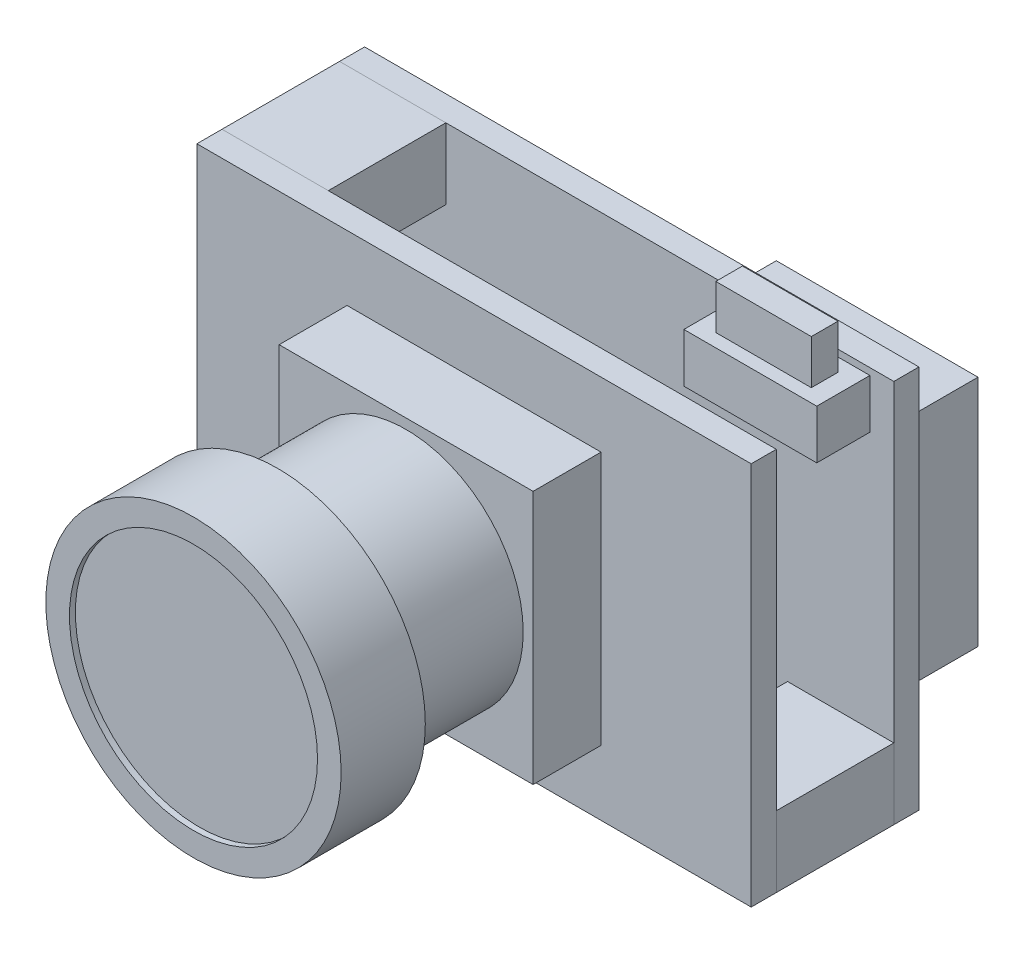
SolidWorks part; units mm, degrees
ref_plane "Front Plane" through (0, 0, 0) normal (0, 0, 1) x (1, 0, 0)
ref_plane "Top Plane" through (0, 0, 0) normal (0, 1, 0) x (1, 0, 0)
ref_plane "Right Plane" through (0, 0, 0) normal (1, 0, 0) x (0, 0, -1)
sketch "Sketch1" plane through (0, 0, 0) normal (0, 0, 1) x (1, 0, 0)
  line L1 (-9.385, 6.5) -> (9.385, 6.5)
  line L2 (-9.385, 6.5) -> (-9.385, -6.5)
  line L3 (-9.385, -6.5) -> (9.385, -6.5)
  line L4 (9.385, 6.5) -> (9.385, -6.5)
  line L5 (-9.385, 6.5) -> (9.385, -6.5) construction
  line L6 (-9.385, -6.5) -> (9.385, 6.5) construction
  point P0 (0, 0)
  dimension "D1" = 13
  dimension "D2" = 18.77
extrude "Boss-Extrude1" add sketch "Sketch1" along normal blind 0.85
sketch "Sketch2" plane through (0, 0, 0.85) normal (0, 0, 1) x (1, 0, 0)
  line L1 (9.385, -6.5) -> (5.785, -6.5)
  line L2 (9.385, -6.5) -> (9.385, -4.1)
  line L3 (9.385, -4.1) -> (5.785, -4.1)
  line L4 (5.785, -6.5) -> (5.785, -4.1)
  line L5 (-9.385, 6.5) -> (-5.785, 6.5)
  line L6 (-9.385, 6.5) -> (-9.385, 4.1)
  line L7 (-9.385, 4.1) -> (-5.785, 4.1)
  line L8 (-5.785, 6.5) -> (-5.785, 4.1)
  dimension "D1" = 2.4
  dimension "D2" = 3.6
extrude "Boss-Extrude2" add sketch "Sketch2" along normal blind 3.98 separate body
sketch "Sketch3" plane through (0, 0, 4.83) normal (0, 0, 1) x (1, 0, 0)
  line L0 (9.385, -6.5) -> (9.385, -4.1) construction
  line L1 (-9.385, 6.5) -> (9.385, 6.5)
  line L2 (-9.385, 6.5) -> (-9.385, -6.5)
  line L3 (-9.385, -6.5) -> (9.385, -6.5)
  line L4 (9.385, 6.5) -> (9.385, -6.5)
  line L5 (5.785, -6.5) -> (9.385, -6.5) construction
  point P4 (0, 0)
  point P6 (0, 0)
  point P8 (0, 0)
  point P9 (-9.385, 6.5)
  point P11 (-9.385, 6.5)
  point P13 (9.385, -6.5)
  point P16 (9.385, -6.5)
extrude "Boss-Extrude3" add sketch "Sketch3" along normal blind 0.85
sketch "Sketch4" plane through (0, 0, 5.68) normal (0, 0, 1) x (1, 0, 0)
  line L1 (-4.3, 4.3) -> (4.3, 4.3)
  line L2 (-4.3, 4.3) -> (-4.3, -4.3)
  line L3 (-4.3, -4.3) -> (4.3, -4.3)
  line L4 (4.3, 4.3) -> (4.3, -4.3)
  line L5 (-4.3, 4.3) -> (4.3, -4.3) construction
  line L6 (-4.3, -4.3) -> (4.3, 4.3) construction
  point P0 (0, 0)
  dimension "D1" = 8.6
extrude "Boss-Extrude4" add sketch "Sketch4" along normal blind 2.3
sketch "Sketch5" plane through (0, 0, 7.98) normal (0, 0, 1) x (1, 0, 0)
  circle A0 centre (0, 0) radius 3.965
  dimension "D1" = 7.93
extrude "Boss-Extrude5" add sketch "Sketch5" along normal blind 4.35
sketch "Sketch6" plane through (0, 0, 12.33) normal (0, 0, 1) x (1, 0, 0)
  circle A0 centre (0, 0) radius 5
  dimension "D1" = 10
extrude "Boss-Extrude6" add sketch "Sketch6" along normal blind 2.85
sketch "Sketch7" plane through (0, 0, 15.18) normal (0, 0, 1) x (1, 0, 0)
  circle A0 centre (0, 0) radius 4.2
  circle A1 centre (0, 0) radius 5 construction
  dimension "D1" = 0.8
extrude "Cut-Extrude1" cut sketch "Sketch7" against normal blind 0.2
sketch "Sketch8" plane through (0, 0, 0) normal (0, 0, -1) x (-1, 0, 0)
  line L0 (-9.385, -6.5) -> (-9.385, 6.5) construction
  line L1 (-9.085, 4.9) -> (-2.255, 4.9)
  line L2 (-9.085, 4.9) -> (-9.085, -3)
  line L3 (-9.085, -3) -> (-2.255, -3)
  line L4 (-2.255, 4.9) -> (-2.255, -3)
  line L5 (-9.385, 6.5) -> (9.385, 6.5) construction
  dimension "D1" = 7.9
  dimension "D2" = 6.83
  dimension "D3" = 0.3
  dimension "D4" = 1.6
extrude "Boss-Extrude7" add sketch "Sketch8" along normal blind 2.3
sketch "Sketch9" plane through (0, 0, 0) normal (0, 0, -1) x (-1, 0, 0)
  line L1 (-0.6481, -5.1764) -> (5.3519, -5.1764)
  line L2 (-0.6481, -5.1764) -> (-0.6481, 0.8236)
  line L3 (-0.6481, 0.8236) -> (5.3519, 0.8236)
  line L4 (5.3519, -5.1764) -> (5.3519, 0.8236)
  dimension "D1" = 6
extrude "Boss-Extrude8" add sketch "Sketch9" along normal blind 1
sketch "Sketch10" plane through (0, 0, 0.85) normal (0, 0, 1) x (1, 0, 0)
  line L1 (8.5749, 6.2701) -> (4.0749, 6.2701)
  line L2 (8.5749, 6.2701) -> (8.5749, 4.6059)
  line L3 (8.5749, 4.6059) -> (4.0749, 4.6059)
  line L4 (4.0749, 6.2701) -> (4.0749, 4.6059)
  dimension "D1" = 4.5
extrude "Boss-Extrude9" add sketch "Sketch10" along normal blind 1.8
sketch "Sketch11" plane through (0, 6.2701, 0) normal (0, 1, 0) x (1, 0, 0)
  line L0 (8.5749, -0.85) -> (4.0749, -2.65) construction
  line L1 (8.5749, -2.65) -> (4.0749, -2.65) construction
  line L2 (4.0749, -2.65) -> (4.0749, -0.85) construction
  line L4 (4.7074, -1.2989) -> (7.9423, -1.2989)
  line L5 (4.7074, -1.2989) -> (4.7074, -2.2011)
  line L6 (4.7074, -2.2011) -> (7.9423, -2.2011)
  line L7 (7.9423, -1.2989) -> (7.9423, -2.2011)
  line L8 (4.7074, -1.2989) -> (7.9423, -2.2011) construction
  line L9 (4.7074, -2.2011) -> (7.9423, -1.2989) construction
  point P7 (6.3249, -1.75)
extrude "Boss-Extrude10" add sketch "Sketch11" along normal blind 1.5
sketch "Sketch12" plane through (0, 0, 0.85) normal (0, 0, 1) x (1, 0, 0)
  line L1 (-3.6639, 1.1451) -> (-6.0818, 1.1451)
  line L2 (-3.6639, 1.1451) -> (-3.6639, -1.1451)
  line L3 (-3.6639, -1.1451) -> (-6.0818, -1.1451)
  line L4 (-6.0818, 1.1451) -> (-6.0818, -1.1451)
  line L5 (-3.6639, 1.1451) -> (-6.0818, -1.1451) construction
  line L6 (-3.6639, -1.1451) -> (-6.0818, 1.1451) construction
  point P0 (-4.8729, 0)
extrude "Boss-Extrude11" add sketch "Sketch12" along normal blind 1.5
sketch "Sketch13" plane through (-6.0818, 0, 0) normal (-1, 0, 0) x (0, 0, 1)
  line L0 (1.6, 1.1451) -> (1.6, -1.1451) construction
  line L1 (2.35, 1.1451) -> (0.85, 1.1451) construction
  line L2 (2.35, -1.1451) -> (0.85, -1.1451) construction
  line L3 (2.35, 0) -> (0.85, 0) construction
  line L4 (2.35, 1.1451) -> (2.35, -1.1451) construction
  line L5 (0.85, 1.1451) -> (0.85, -1.1451) construction
  circle A0 centre (1.6, 0.55) radius 0.45
  circle A1 centre (1.6, -0.55) radius 0.45
  point P16 (1.6, 0.5433)
  dimension "D1" = 0.9
  dimension "D2" = 1.1
extrude "Boss-Extrude13" add sketch "Sketch13" along normal blind 4
